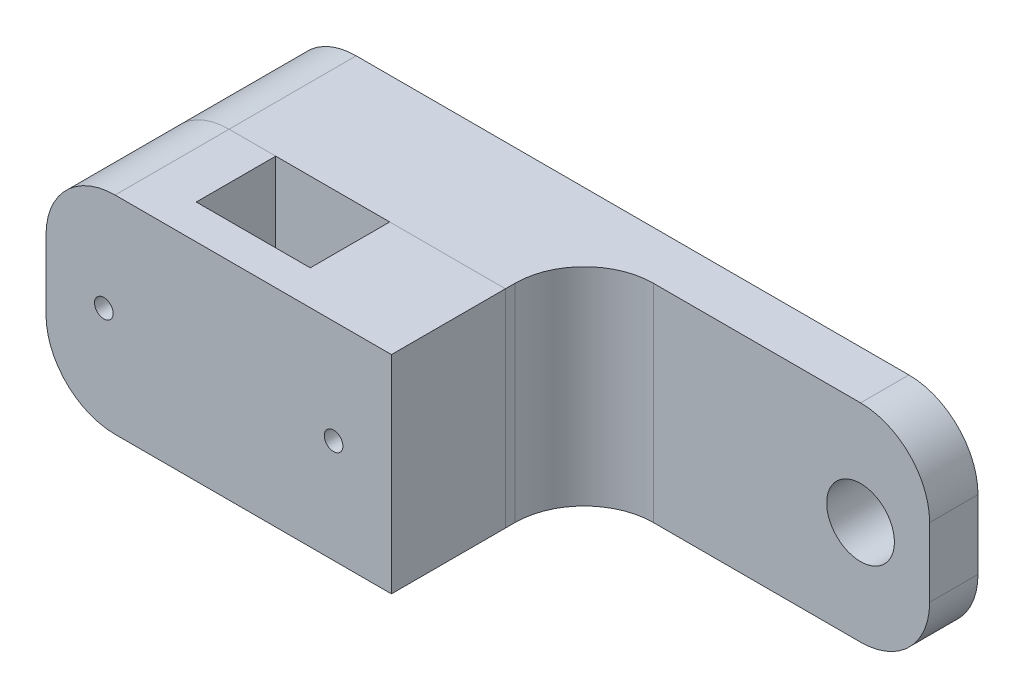
SolidWorks part; units mm, degrees
ref_plane "Front Plane" through (0, 0, 0) normal (0, 0, 1) x (1, 0, 0)
ref_plane "Top Plane" through (0, 0, 0) normal (0, 1, 0) x (1, 0, 0)
ref_plane "Right Plane" through (0, 0, 0) normal (1, 0, 0) x (0, 0, -1)
sketch "Sketch1" plane through (0, 0, 0) normal (0, 0, 1) x (1, 0, 0)
  line L0 (50, 0) -> (50, 30)
  line L1 (0, 0) -> (100, 0)
  line L2 (0, 0) -> (0, 30)
  line L3 (0, 30) -> (100, 30)
  line L4 (100, 0) -> (100, 30)
  line L5 (100, 15) -> (90, 15) construction
  circle A0 centre (90, 15) radius 4.9
  dimension "D1" = 100
  dimension "D2" = 30
extrude "Boss-Extrude1" add sketch "Sketch1" along normal blind 18.4 contours L3 L2 L1 L0 region at (25, 15, 0)
extrude "Boss-Extrude2" add sketch "Sketch1<3>" along normal blind 7 contours L1 L4 L3 L0 region at (74.2058, 15, 0)
sketch "Sketch1<3>" plane through (0, 0, 0) normal (0, 0, 1) x (1, 0, 0) same geometry as "Sketch1"
sketch "Sketch2" plane through (0, 0, 18.4) normal (0, 0, 1) x (1, 0, 0)
  line L0 (16.75, 30) -> (16.75, 0)
  line L1 (0, 30) -> (50, 30)
  line L2 (0, 30) -> (0, 0)
  line L3 (0, 0) -> (50, 0)
  line L4 (50, 30) -> (50, 0)
  line L5 (33.25, 0) -> (33.25, 30)
  line L6 (16.75, 15) -> (0, 15) construction
  line L7 (33.25, 15) -> (50, 15) construction
  circle A0 centre (8.375, 15) radius 1.35
  circle A1 centre (41.625, 15) radius 1.35
  line M11 (50, 30) -> (0, 30)
  line M12 (0, 30) -> (0, 0)
  line M13 (0, 0) -> (50, 0)
  line M14 (50, 0) -> (50, 30)
  dimension "D1" = 16.5
extrude "Cut-Extrude1" cut sketch "Sketch2" against normal blind 27 contours A0 | A1 region at (8.375, 15, 18.4) region at (41.625, 15, 18.4)
extrude "Boss-Extrude3" add sketch "Sketch2<3>" along normal blind 11.5 separate body contours L0 A0 M11 M12 M13 | L5 L3 A1 M14 M11 region at (16.4064, 15, 18.4) region at (41.625, 29.6564, 18.4)
sketch "Sketch2<3>" plane through (0, 0, 18.4) normal (0, 0, 1) x (1, 0, 0) same geometry as "Sketch2"
sketch "Sketch3" plane through (0, 0, 29.9) normal (0, 0, 1) x (1, 0, 0)
  line L1 (0, 0) -> (50, 0)
  line L2 (0, 0) -> (0, 30)
  line L3 (0, 30) -> (50, 30)
  line L4 (50, 0) -> (50, 30)
  circle A0 centre (8.375, 15) radius 1.35
  circle A1 centre (41.625, 15) radius 1.35
extrude "Boss-Extrude4" add sketch "Sketch3" along normal blind 5
fillet "Fillet1" radius 10 5 edges at (0, 30, 9.2) (0, 0, 9.2) (100, 30, 3.5) (100, 0, 3.5) (50, 15, 7)
fillet "Fillet2" radius 10 2 edges at (0, 30, 26.65) (0, 0, 26.65)
